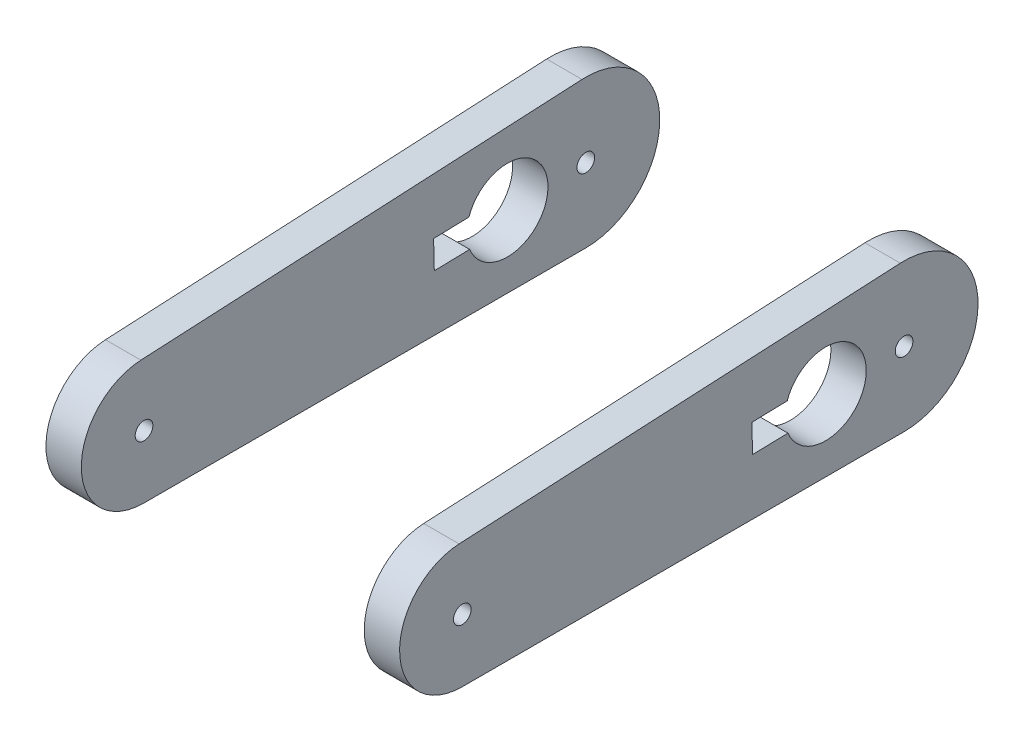
SolidWorks part; units mm, degrees
ref_plane "Front Plane" through (0, 0, 0) normal (0, 0, 1) x (1, 0, 0)
ref_plane "Top Plane" through (0, 0, 0) normal (0, 1, 0) x (1, 0, 0)
ref_plane "Right Plane" through (0, 0, 0) normal (1, 0, 0) x (0, 0, -1)
ref_plane "Plane1" through (50.8, 0, 0) normal (1, 0, 0) x (0, 0, -1)
sketch "Sketch1" plane through (50.8, 0, 0) normal (1, 0, 0) x (0, 0, -1)
  line L0 (-158.647, -4.0425) -> (-1.5131, -0.0386) construction
  line L1 (-159.4706, 12.1066) -> (-1.0294, 20.1864) construction
  line L2 (-158.647, -20.2127) -> (0, -20.2127) construction
  line L3 (-159.794, 18.4484) -> (-1.3528, 26.5282)
  line L4 (-158.647, -26.5627) -> (0, -26.5627)
  circle A0 centre (0, 0) radius 29.845 construction
  circle A1 centre (-158.647, -4.0425) radius 23.622 construction
  arc A2 (-159.4706, 12.1066) -> (-158.647, -20.2127) centre (-158.647, -4.0425) ccw construction
  arc A3 (0, -20.2127) -> (-1.0294, 20.1864) centre (0, 0) ccw construction
  arc A4 (0, -26.5627) -> (-1.3528, 26.5282) centre (0, 0) ccw
  arc A5 (-159.794, 18.4484) -> (-158.647, -26.5627) centre (-158.647, -4.0425) ccw
  circle A6 centre (-158.647, -4.0425) radius 3.175
  circle A7 centre (0, 0) radius 3.175
  dimension "D1" = 59.69
  dimension "D2" = 47.244
  dimension "D3" = 40.4254
  dimension "D4" = 32.3403
  dimension "D8" = 6.35
  dimension "D6" = 157.1849
  dimension "D7" = 6.35
extrude "Boss-Extrude1" add sketch "Sketch1" along normal blind 12.7
sketch "Sketch2" plane through (63.5, 0, 0) normal (1, 0, 0) x (0, 0, -1)
  line L0 (-158.647, -4.0425) -> (0, 0) construction
  line L2 (-41.7062, -6.146) -> (-54.4062, -6.4696)
  line L3 (-41.9651, 4.014) -> (-54.6651, 3.6904)
  line L4 (-54.4062, -6.4696) -> (-54.6651, 3.6904)
  circle A0 centre (0, 0) radius 23.8125 construction
  circle A1 centre (-28.169, -0.7178) radius 4.3656 construction
  arc A2 (-41.7062, -6.146) -> (-41.9651, 4.014) centre (-28.169, -0.7178) ccw
  point P5 (-41.7318, 3.7539)
  point P11 (-53.8636, 4.6245)
  dimension "D1" = 8.7312
  dimension "D2" = 47.625
  dimension "D3" = 29.17
  dimension "D4" = 10.16
  dimension "D5" = 12.7
extrude "Cut-Extrude1" cut sketch "Sketch2" against normal up to surface (12.7 mm away) up to face at (50.8, -2.0035, 78.6257)
mirror "Mirror2" about plane through (0, 0, 0) normal (1, 0, 0) of bodies 102
equation "\"D3@Sketch1\"=0.2 * 25 /pi"
equation "\"D4@Sketch1\"=0.2 * 20 / pi"
equation "\"D1@Sketch2\"=11/32"
equation "\"D2@Sketch2\"=60/32"
equation "\"D3@Sketch2\"=27.9mm + .05in"
